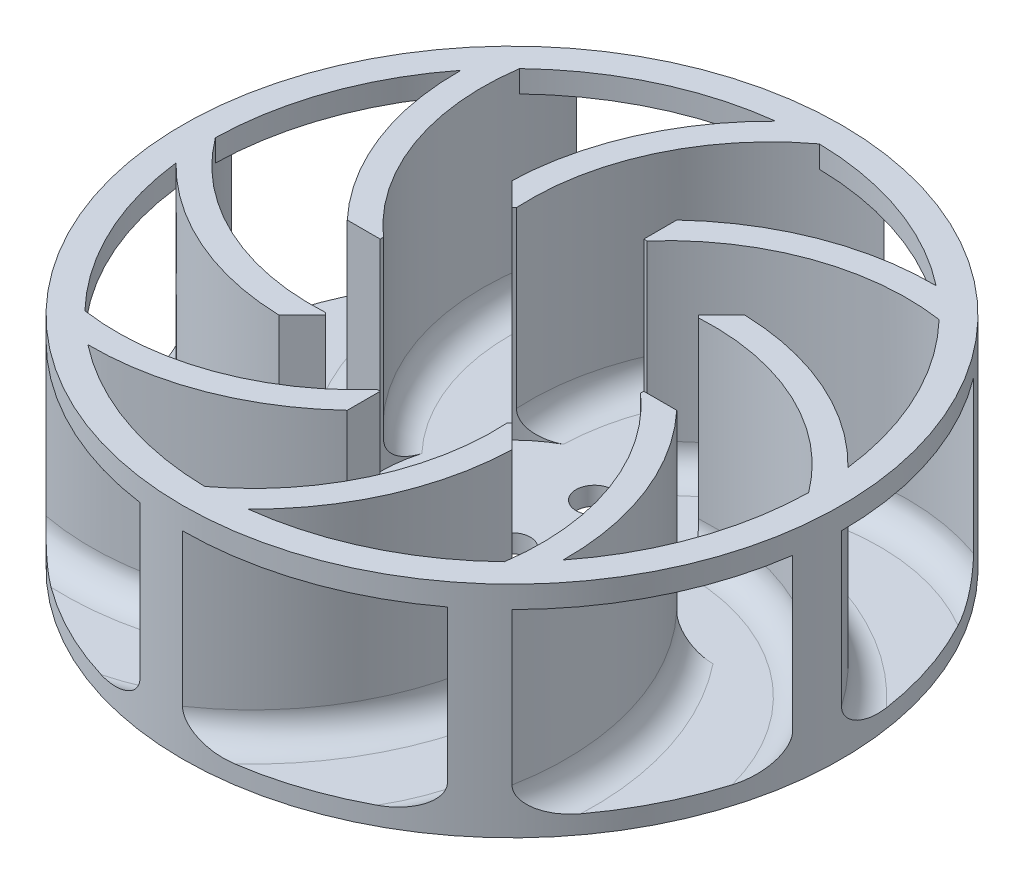
SolidWorks part; units mm, degrees
ref_plane "前视基准面" through (0, 0, 0) normal (0, 0, 1) x (1, 0, 0)
ref_plane "上视基准面" through (0, 0, 0) normal (0, 1, 0) x (1, 0, 0)
ref_plane "右视基准面" through (0, 0, 0) normal (1, 0, 0) x (0, 0, -1)
sketch "草图1" plane through (0, 0, 0) normal (0, 1, 0) x (1, 0, 0)
  line L0 (-0.469, 0.45) -> (0.469, 0.45)
  circle A0 centre (0, 0) radius 18
  arc A1 (-0.469, 0.45) -> (0.469, 0.45) centre (0, 0) ccw
  dimension "D1" = 1.3
  dimension "D2" = 1.3
  dimension "D3" = 0.45
extrude "凸台-拉伸1" add sketch "草图1" against normal blind 1
sketch "草图3" plane through (0, -1, 0) normal (0, -1, 0) x (-1, 0, 0)
  line L0 (-0.469, 0.45) -> (0.469, 0.45)
  arc A0 (-0.469, 0.45) -> (0.469, 0.45) centre (0, 0) ccw
  circle A1 centre (0, 0) radius 1.5
extrude "凸台-拉伸2" add sketch "草图3" against normal blind 5
sketch "草图4" plane through (0, -1, 0) normal (0, -1, 0) x (-1, 0, 0)
  line L0 (0, 0) -> (0, -18) construction
  line L1 (0, 0) -> (0, 18) construction
  line L2 (0, 0) -> (18, 0) construction
  line L3 (0, 0) -> (-18, 0) construction
  line L6 (0, 0) -> (12.7279, -12.7279) construction
  line L7 (0, 0) -> (-12.7279, 12.7279) construction
  line L8 (0, -9) -> (0, -7)
  line L9 (-6.364, -6.364) -> (-4.9497, -4.9497)
  line L10 (-9, 0) -> (-7, 0)
  line L11 (-6.364, 6.364) -> (-4.9497, 4.9497)
  line L12 (0, 9) -> (0, 7)
  line L13 (6.364, 6.364) -> (4.9497, 4.9497)
  line L14 (9, 0) -> (7, 0)
  line L15 (6.364, -6.364) -> (4.9497, -4.9497)
  circle A0 centre (0, 0) radius 18 construction
  arc A2 (12.7279, -12.7279) -> (0, -9) centre (10.0296, 1.6515) cw
  arc A4 (14.3687, -10.8417) -> (0, -7) centre (9.9812, 1.5401) cw
  arc A6 (12.7279, -12.7279) -> (14.3687, -10.8417) centre (0, 0) ccw
  arc A7 (0, -18) -> (-6.364, -6.364) centre (8.2598, -5.9243) cw
  arc A8 (2.494, -17.8264) -> (-4.9497, -4.9497) centre (8.1468, -5.9688) cw
  arc A9 (0, -18) -> (2.494, -17.8264) centre (0, 0) ccw
  arc A10 (-12.7279, -12.7279) -> (-9, 0) centre (1.6515, -10.0296) cw
  arc A11 (-10.8417, -14.3687) -> (-7, 0) centre (1.5401, -9.9812) cw
  arc A12 (-12.7279, -12.7279) -> (-10.8417, -14.3687) centre (0, 0) ccw
  arc A13 (-18, 0) -> (-6.364, 6.364) centre (-5.9243, -8.2598) cw
  arc A14 (-17.8264, -2.494) -> (-4.9497, 4.9497) centre (-5.9688, -8.1468) cw
  arc A15 (-18, 0) -> (-17.8264, -2.494) centre (0, 0) ccw
  arc A16 (-12.7279, 12.7279) -> (0, 9) centre (-10.0296, -1.6515) cw
  arc A17 (-14.3687, 10.8417) -> (0, 7) centre (-9.9812, -1.5401) cw
  arc A18 (-12.7279, 12.7279) -> (-14.3687, 10.8417) centre (0, 0) ccw
  arc A19 (0, 18) -> (6.364, 6.364) centre (-8.2598, 5.9243) cw
  arc A20 (-2.494, 17.8264) -> (4.9497, 4.9497) centre (-8.1468, 5.9688) cw
  arc A21 (0, 18) -> (-2.494, 17.8264) centre (0, 0) ccw
  arc A22 (12.7279, 12.7279) -> (9, 0) centre (-1.6515, 10.0296) cw
  arc A23 (10.8417, 14.3687) -> (7, 0) centre (-1.5401, 9.9812) cw
  arc A24 (12.7279, 12.7279) -> (10.8417, 14.3687) centre (0, 0) ccw
  arc A25 (18, 0) -> (6.364, -6.364) centre (5.9243, 8.2598) cw
  arc A26 (17.8264, 2.494) -> (4.9497, -4.9497) centre (5.9688, 8.1468) cw
  arc A27 (18, 0) -> (17.8264, 2.494) centre (0, 0) ccw
  point P14 (0, 0)
  point P17 (-8.7356, 4.2214)
  dimension "D5" = 2.5
  dimension "D3" = 8
  dimension "D4" = 2
  dimension "D1" = 45
  dimension "D2" = 45
extrude "凸台-拉伸3" add sketch "草图4" against normal blind 11 from surface starting at face at (0, 0, 1.5)
fillet "圆角1" radius 1.5 17 edges at (0, 0, 1.5) (12.9445, 0, -4.5762) (12.389, 0, 5.9173) (3.2258, 0, 12.543) (-6.5883, 0, 11.1503) (-12.543, 0, 3.2258) (-11.1503, 0, -6.5883) (-4.5762, 0, -12.9445) (-3.2258, 0, -12.543) (-12.389, 0, -5.9173) (-12.9445, 0, 4.5762) (-5.9173, 0, 12.389) (4.5762, 0, 12.9445) (11.1503, 0, 6.5883) (12.543, 0, -3.2258) (6.5883, 0, -11.1503) (5.9173, 0, -12.389)
sketch "草图5" plane through (0, -1, 0) normal (0, -1, 0) x (1, 0, 0)
  line L0 (-0.469, -0.45) -> (0.469, -0.45)
  arc A0 (0.469, -0.45) -> (-0.469, -0.45) centre (0, 0) ccw
  circle A1 centre (0, 0) radius 2
sketch "草图6" plane through (0, 0, 0) normal (0, 1, 0) x (1, 0, 0)
  circle A0 centre (0, 0) radius 7.2
extrude "切除-拉伸1" cut sketch "草图6" along normal through all
sketch "草图7" plane through (0, 0, 0) normal (0, 1, 0) x (1, 0, 0)
  circle A0 centre (0, 0) radius 1
  circle A1 centre (0, 4.5) radius 1
  circle A2 centre (4.5, 0) radius 1
  circle A3 centre (0, -4.5) radius 1
  circle A4 centre (-4.5, 0) radius 1
  point P14 (0, 0)
  dimension "D1" = 4.5
  dimension "D2" = 4
extrude "切除-拉伸2" cut sketch "草图7" against normal through all both and the other way through all
sketch "草图8" plane through (0, 11, 0) normal (0, 1, 0) x (1, 0, 0)
  circle A0 centre (0, 0) radius 18
  circle A1 centre (0, 0) radius 16.5
  dimension "D1" = 1.5
  dimension "D2" = 36
extrude "凸台-拉伸4" add sketch "草图8" against normal blind 1.2
